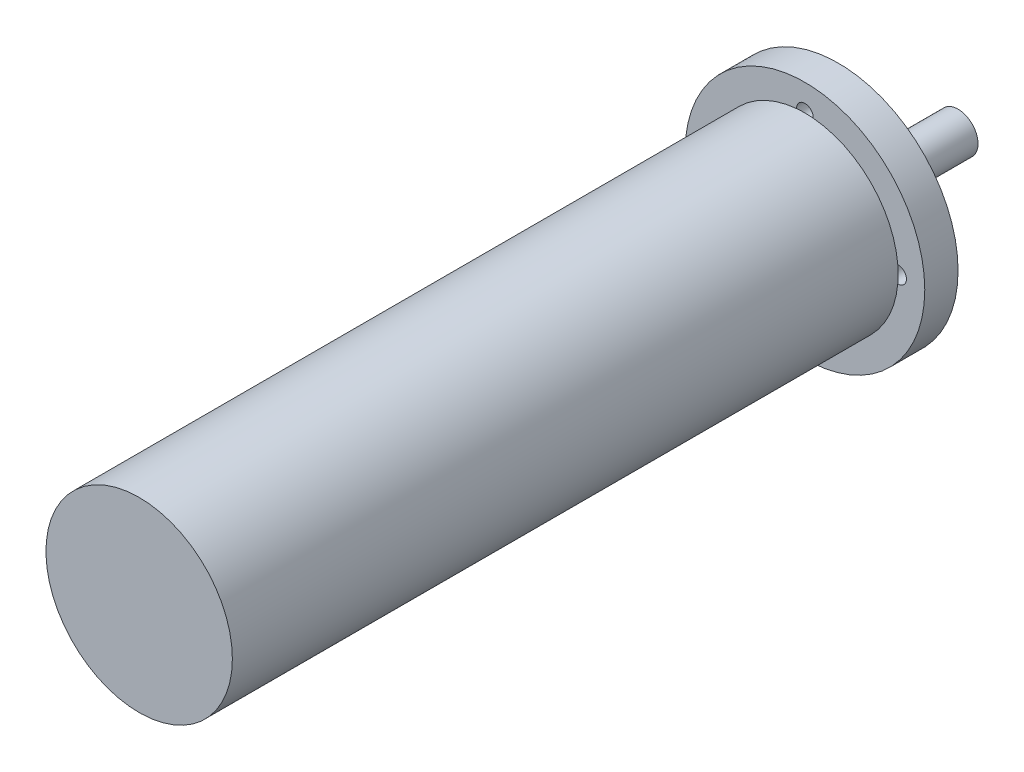
SolidWorks part; units mm, degrees
ref_plane "Front Plane" through (0, 0, 0) normal (0, 0, 1) x (1, 0, 0)
ref_plane "Top Plane" through (0, 0, 0) normal (0, 1, 0) x (1, 0, 0)
ref_plane "Right Plane" through (0, 0, 0) normal (1, 0, 0) x (0, 0, -1)
sketch "Sketch1" plane through (0, 0, 0) normal (0, 0, 1) x (1, 0, 0)
  circle A0 centre (0, 0) radius 14
  dimension "D1" = 28
extrude "Boss-Extrude1" add sketch "Sketch1" along normal blind 100
sketch "Sketch2" plane through (0, 0, 0) normal (0, 0, -1) x (-1, 0, 0)
  circle A0 centre (0, 0) radius 11
  circle A1 centre (0, 0) radius 3
  circle A2 centre (0, 0) radius 18
  circle M1 centre (0, 0) radius 14
  dimension "D1" = 22
  dimension "D2" = 6
  dimension "D3" = 36
extrude "Boss-Extrude2" add sketch "Sketch2" along normal blind 7 contours A0 A1 | A1 region at (10.6889, 0, 0) region at (0, 0, 0)
extrude "Boss-Extrude3" add sketch "Sketch2<3>" along normal blind 23 contours A1 region at (0, 0, 0)
sketch "Sketch2<3>" plane through (0, 0, 0) normal (0, 0, -1) x (-1, 0, 0) same geometry as "Sketch2"
extrude "Boss-Extrude4" add sketch "Sketch2<4>" along normal blind 5 contours A2 M1 | A0 M1 region at (17.4909, 0, 0) region at (13.604, 0, 0)
sketch "Sketch2<4>" plane through (0, 0, 0) normal (0, 0, -1) x (-1, 0, 0) same geometry as "Sketch2"
sketch "Sketch3" plane through (0, 0, -5) normal (0, 0, -1) x (-1, 0, 0)
  circle A0 centre (0, 0) radius 14 construction
  dimension "D1" = 28
hole_wizard "M3x0.5 Tapped Hole1" positions "Sketch6" profile "Sketch7" tap size "M3x0.5" standard "ANSI Metric" end condition up to next
sketch "Sketch6" plane through (0, 0, -5) normal (0, 0, -1) x (-1, 0, 0)
  line L0 (0, 55) -> (0, -55) construction
  line L1 (55, 0) -> (-55, 0) construction
  circle A0 centre (0, 0) radius 14 construction
  point P0 (0, 14)
  point P6 (14, 0)
  point P10 (0, -14)
  point P12 (-14, 0)
cosmetic thread "Hole Thread1" parameters "D2"=3
cosmetic thread "Hole Thread2" parameters "D2"=3
cosmetic thread "Hole Thread3" parameters "D2"=3
cosmetic thread "Hole Thread4" parameters "D2"=3
sketch "Sketch7" plane through (0, 14, -5) normal (1, 0, 0) x (0, 1, 0)
  line L0 (0, 0) -> (0, 5)
  line L1 (0, 5) -> (1.25, 5)
  line L2 (1.25, 5) -> (1.25, 0)
  line L5 (1.25, 0) -> (0, 0)
  line L11 (0, -6.35) -> (0, 107.95) construction
  dimension "Thru Tap Drill Dia." = 2.5
  dimension "Thru Tap Drill Depth" = 5
